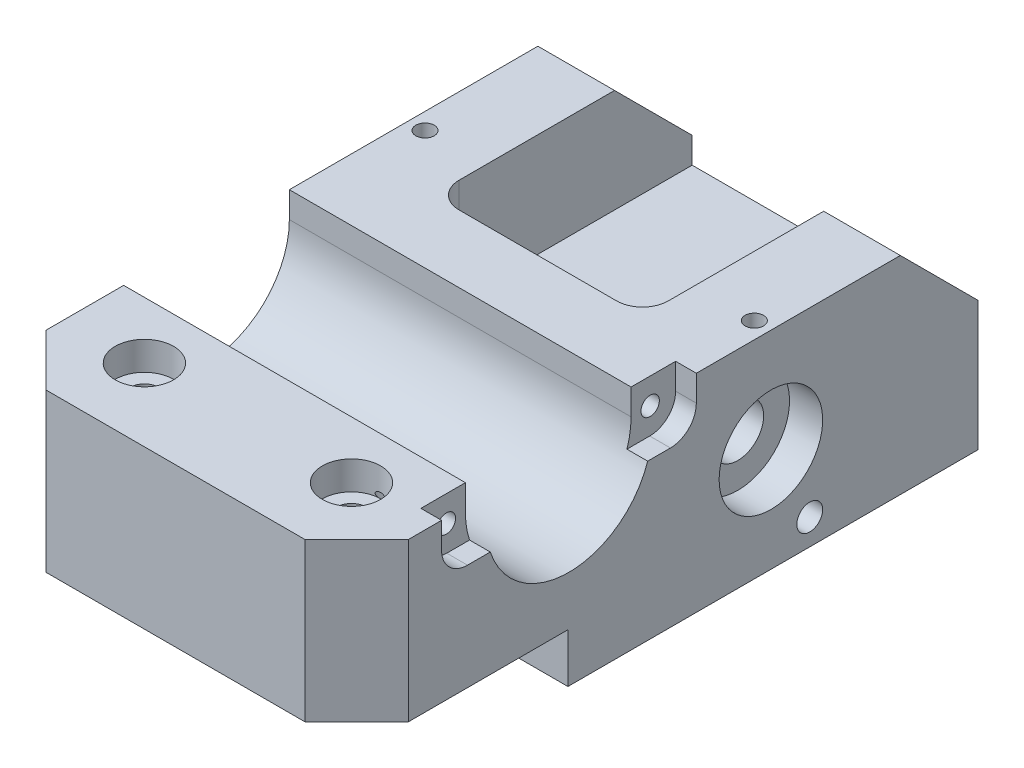
SolidWorks part; units mm, degrees
material "Nylon 6/10"
ref_plane "Front Plane" through (0, 0, 0) normal (0, 0, 1) x (1, 0, 0)
ref_plane "Top Plane" through (0, 0, 0) normal (0, 1, 0) x (1, 0, 0)
ref_plane "Right Plane" through (0, 0, 0) normal (1, 0, 0) x (0, 0, -1)
sketch "Sketch1" plane through (0, 0, 0) normal (0, 1, 0) x (1, 0, 0)
  line L1 (-22.225, -38.1) -> (22.225, -38.1)
  line L2 (-22.225, -38.1) -> (-22.225, 38.1)
  line L3 (-22.225, 38.1) -> (22.225, 38.1)
  line L4 (22.225, -38.1) -> (22.225, 38.1)
  line L5 (-22.225, -38.1) -> (22.225, 38.1) construction
  line L6 (-22.225, 38.1) -> (22.225, -38.1) construction
  point P0 (0, 0)
  dimension "D1" = 44.45
  dimension "D2" = 76.2
extrude "Base" add sketch "Sketch1" along normal blind 12.7 and the other way blind 12.7
sketch "Sketch2" plane through (0, 0, -38.1) normal (0, 0, -1) x (-1, 0, 0)
  line L1 (-22.225, -12.7) -> (22.225, -12.7) construction
  circle A0 centre (0, -12.7) radius 4.7625
  dimension "D1" = 9.525
extrude "ShaftGuide" cut sketch "Sketch2" against normal blind 25.4
ref_plane "Plane1" through (0, -12.7, 0) normal (0, -1, 0) x (-1, 0, 0)
sketch "Sketch3" plane through (0, -12.7, 0) normal (0, -1, 0) x (-1, 0, 0)
  line L0 (10.922, -12.192) -> (16.002, -12.192)
  line L1 (22.225, -38.1) -> (-22.225, -38.1) construction
  line L2 (-22.225, -38.1) -> (-22.225, 38.1) construction
  line L3 (0, 0) -> (0, 102.0916) construction
  line L5 (-10.922, -12.192) -> (-10.922, 4.572)
  line L6 (-22.225, -38.1) -> (22.225, -38.1)
  line L7 (-10.922, 4.572) -> (10.922, 4.572)
  line L8 (10.922, -12.192) -> (10.922, 4.572)
  line L10 (-10.922, -12.192) -> (-22.225, -12.192)
  line L11 (-22.225, -38.1) -> (-22.225, -12.192)
  line L13 (22.225, -38.1) -> (22.225, -12.192)
  line L14 (4.7625, 38.1) -> (4.7625, 12.7)
  line L15 (4.7625, 12.7) -> (-4.7625, 12.7)
  line L16 (-4.7625, 12.7) -> (-4.7625, 38.1)
  line L17 (-4.7625, 38.1) -> (-22.225, 38.1)
  line L18 (-22.225, 38.1) -> (-22.225, -38.1)
  line L19 (-22.225, -38.1) -> (22.225, -38.1)
  line L20 (22.225, -38.1) -> (22.225, 38.1)
  line L21 (22.225, 38.1) -> (4.7625, 38.1)
  line L23 (22.225, 38.1) -> (22.225, -38.1) construction
  line L25 (-4.7625, 38.1) -> (-22.225, 38.1) construction
  line L26 (22.225, -12.192) -> (16.002, -12.192)
  line L28 (22.225, -38.1) -> (22.225, 38.1) construction
  line L29 (22.225, 38.1) -> (4.7625, 38.1) construction
  dimension "D6" = 21.844
  dimension "D3" = 33.528
  dimension "D7" = 16.764
  dimension "D1" = 0
extrude "ActuatorPlaneCut" cut sketch "Sketch3" against normal blind 6.0325
sketch "Sketch5" plane through (0, 0, 0) normal (0, 1, 0) x (1, 0, 0)
  line L1 (12.827, 19.05) -> (-12.827, 19.05)
  line L2 (12.827, 6.35) -> (12.827, 19.05)
  line L3 (12.827, 6.35) -> (-12.827, 6.35)
  line L4 (0, 0) -> (0, 121.8983) construction
  line L5 (-10.922, 4.572) -> (10.922, 4.572) construction
  line L6 (-12.827, 6.35) -> (-12.827, 19.05)
  point P17 (12.827, 6.35)
  point P20 (12.827, 19.05)
  dimension "D3" = 1.778
  dimension "D1" = 12.7
  dimension "D2" = 25.654
extrude "CenterSlot" cut sketch "Sketch5" along normal through all and the other way through all
fillet "CenterSlotFillet" radius 3.175 4 edges at (-12.827, 0, -19.05) (-12.827, 0, -6.35) (12.827, 0, -6.35) (12.827, 0, -19.05)
sketch "Sketch40" plane through (0, -12.7, 0) normal (0, -1, 0) x (1, 0, 0)
  line L1 (10.922, -8.89) -> (-10.922, -8.89)
  line L2 (10.922, -8.89) -> (10.922, 9.017)
  line L3 (7.747, 12.192) -> (-7.747, 12.192)
  line L4 (-10.922, -8.89) -> (-10.922, 9.017)
  line L6 (10.922, -4.572) -> (10.922, 12.192) construction
  line L7 (-9.652, -6.35) -> (9.652, -6.35) construction
  arc A0 (-7.747, 12.192) -> (-10.922, 9.017) centre (-7.747, 9.017) ccw
  arc A1 (7.747, 12.192) -> (10.922, 9.017) centre (7.747, 9.017) cw
  point P8 (-10.922, 12.192)
  dimension "D1" = 3.175
  dimension "D2" = 2.54
extrude "GearBoxPit" cut sketch "Sketch40" against normal blind 11.176
sketch "Sketch60" plane through (0, 12.7, 0) normal (0, 1, 0) x (1, 0, 0)
  line L0 (22.225, 38.1) -> (-22.225, 38.1) construction
  line L1 (-12.827, 15.875) -> (12.827, 15.875)
  line L2 (-12.827, 15.875) -> (-12.827, 38.1)
  line L3 (-12.827, 38.1) -> (12.827, 38.1)
  line L4 (12.827, 15.875) -> (12.827, 38.1)
  line L5 (12.827, 9.525) -> (12.827, 15.875) construction
extrude "FrontCutaway" cut sketch "Sketch60" against normal blind 12.7
chamfer "ChamferFront" distance 9.525 angle 45 2 edges at (-17.526, 12.7, -38.1) (17.526, 12.7, -38.1)
sketch "Sketch67" plane through (0, -12.7, 0) normal (0, -1, 0) x (-1, 0, 0)
  line L0 (-12.3825, 2.54) -> (12.3825, 2.54) construction
  line L1 (-12.3825, 2.9369) -> (12.3825, 2.9369)
  line L2 (-12.3825, 2.1431) -> (12.3825, 2.1431)
  line L3 (-12.3825, -8.128) -> (12.3825, -8.128) construction
  line L4 (-12.3825, -7.7311) -> (12.3825, -7.7311)
  line L5 (-12.3825, -8.5249) -> (12.3825, -8.5249)
  line L6 (9.652, 6.35) -> (-9.652, 6.35) construction
  line L7 (0, 0.0055) -> (0, 0.7987) construction
  arc A0 (-12.3825, 2.9369) -> (-12.3825, 2.1431) centre (-12.3825, 2.54) ccw
  arc A1 (12.3825, 2.1431) -> (12.3825, 2.9369) centre (12.3825, 2.54) ccw
  arc A2 (-12.3825, -7.7311) -> (-12.3825, -8.5249) centre (-12.3825, -8.128) ccw
  arc A3 (12.3825, -8.5249) -> (12.3825, -7.7311) centre (12.3825, -8.128) ccw
  point P2 (0, 2.54)
  point P9 (0, -8.128)
  dimension "D1" = 0.7937
  dimension "D2" = 3.81
  dimension "D3" = 24.765
  dimension "D4" = 10.668
extrude "GearBoxSlotsH" cut sketch "Sketch67" against normal blind 2.286
sketch "Sketch55" plane through (-22.225, 0, 0) normal (-1, 0, 0) x (0, 0, 1)
  line L0 (-38.1, -12.7) -> (12.192, -12.7) construction
  line L1 (-19.05, -12.7) -> (-19.05, -7.9375) construction
  circle A0 centre (-17.4625, -9.525) radius 1.5875
  dimension "D1" = 3.175
  dimension "D2" = 3.175
extrude "GuideBarHole" cut sketch "Sketch55" against normal through all
sketch "Sketch56" plane through (0, 0, 0) normal (1, 0, 0) x (0, 0, -1)
  line L0 (15.875, -12.7) -> (9.525, -12.7) construction
  line L1 (15.875, -12.7) -> (9.525, -12.7) construction
  line L2 (12.7, -12.7) -> (12.7, 12.7) construction
  line L3 (28.575, 12.7) -> (-38.1, 12.7) construction
  circle A0 centre (12.7, 0) radius 3.175
  dimension "D1" = 6.35
extrude "PitchShaftHole" cut sketch "Sketch56" against normal through all and the other way through all
sketch "Sketch57" plane through (-22.225, 0, 0) normal (-1, 0, 0) x (0, 0, 1)
  circle A0 centre (-12.7, 0) radius 6.35
  circle A1 centre (-12.7, 0) radius 3.175 construction
  dimension "D1" = 12.7
extrude "BearingBoreR" cut sketch "Sketch57" against normal blind 4.064
mirror "BearingBoreL" about plane through (0, 0, 0) normal (1, 0, 0) of "BearingBoreR"
hole_wizard "BearingBoreSetScrews" positions "Sketch59" profile "Sketch58" tap size "#4-40" standard "ANSI Inch" end condition up to next
sketch "Sketch59" plane through (4.3433, 12.7, -10.3044) normal (0, 1, 0) x (1, 0, 0)
  line L5 (-26.5683, 8.7456) -> (-26.5683, -3.9544) construction
  line L6 (-26.5683, 8.7456) -> (-26.5683, -3.9544) construction
  line L7 (-26.5683, 2.3956) -> (17.8817, 2.3956) construction
  line L8 (17.8817, -48.4044) -> (17.8817, 18.2706) construction
  line L10 (-26.5683, 18.2706) -> (-26.5683, -48.4044) construction
  point P0 (-24.5363, 2.3956)
  point P2 (15.8497, 2.3956)
  dimension "D1" = 2.032
  dimension "D2" = 2.032
sketch "Sketch58" plane through (-20.193, 12.7, -12.7) normal (1, 0, 0) x (0, 0, 1)
  line L0 (0, 0) -> (0, 6.35)
  line L1 (0, 6.35) -> (1.1303, 6.35)
  line L2 (1.1303, 6.35) -> (1.1303, 0)
  line L5 (1.1303, 0) -> (0, 0)
  line L11 (0, -6.35) -> (0, 107.95) construction
  dimension "Thru Tap Drill Dia." = 2.2606
  dimension "Thru Tap Drill Depth" = 6.35
cosmetic thread "Hole Thread18" parameters "D2"=2.8448
cosmetic thread "Hole Thread19" parameters "D2"=2.8448
hole_wizard "ToggleAssemHoles" positions "Sketch50" profile "Sketch49" tap size "#6-32" standard "ANSI Inch"
sketch "Sketch50" plane through (0, -12.7, 0) normal (0, -1, 0) x (-1, 0, 0)
  line L1 (4.7625, 38.1) -> (-4.7625, 38.1) construction
  line L2 (0, 0) -> (0, 49.3678) construction
  line L3 (-9.652, 19.05) -> (-4.7625, 19.05) construction
  point P0 (12.7, 31.75)
  point P2 (-12.7, 31.75)
  point P8 (0, 38.1)
  dimension "D1" = 12.7
  dimension "D2" = 12.7
sketch "Sketch49" plane through (-12.7, -12.7, -31.75) normal (1, 0, 0) x (0, 0, -1)
  line L0 (0, 0) -> (0, 10.2107)
  line L1 (0, 10.2107) -> (1.3525, 9.398)
  line L2 (1.3525, 9.398) -> (1.3525, 0)
  line L5 (1.3525, 0) -> (0, 0)
  line L10 (0, 10.2107) -> (-1.3526, 9.398) construction
  line L11 (0, -6.35) -> (0, 107.95) construction
  dimension "Tap Drill Dia." = 2.7051
  dimension "Tap Drill Depth" = 9.398
  dimension "Drill Angle" = 118
cosmetic thread "Hole Thread12" parameters "D1"=9.398, "D2"=3.5052
cosmetic thread "Hole Thread13" parameters "D1"=9.398, "D2"=3.5052
chamfer "BackChamfers" distance 6.35 angle 45 2 edges at (22.225, 3.0162, 38.1) (-22.225, 3.0162, 38.1)
sketch "Sketch62" plane through (-22.225, 0, 0) normal (-1, 0, 0) x (0, 0, 1)
  line L0 (-38.1, -12.7) -> (-38.1, 3.175) construction
  line L1 (-28.575, 12.7) -> (31.75, 12.7) construction
  line L2 (1.905, 9.525) -> (1.905, 12.7)
  line L3 (22.225, 9.525) -> (22.225, 12.7)
  line L4 (22.225, 12.7) -> (1.905, 12.7)
  arc A0 (1.905, 9.525) -> (22.225, 9.525) centre (12.065, 9.525) ccw
  dimension "D1" = 20.32
  dimension "D2" = 50.165
  dimension "D3" = 3.175
extrude "PitchMotorSlot" cut sketch "Sketch62" against normal through all
sketch "Sketch63" plane through (22.225, 0, 0) normal (-1, 0, 0) x (0, 0, 1)
  line L1 (-3.556, 12.7) -> (27.686, 12.7)
  line L2 (-3.556, 12.7) -> (-3.556, 9.525)
  line L3 (-0.381, 6.35) -> (24.511, 6.35)
  line L4 (27.686, 12.7) -> (27.686, 9.525)
  line L5 (22.225, 12.7) -> (1.905, 12.7) construction
  arc A0 (24.511, 6.35) -> (27.686, 9.525) centre (24.511, 9.525) ccw
  arc A1 (-0.381, 6.35) -> (-3.556, 9.525) centre (-0.381, 9.525) cw
  point P4 (12.065, 12.7)
  dimension "D3" = 3.175
  dimension "D1" = 31.242
  dimension "D2" = 6.35
extrude "PitchMotorMountingSlots" cut sketch "Sketch63" along normal blind 2.54
hole_wizard "PitchMotorMountingHoles" positions "Sketch65" profile "Sketch64" tap size "#4-40" standard "ANSI Inch"
sketch "Sketch65" plane through (19.685, 0, 0) normal (1, 0, 0) x (0, 0, -1)
  line L0 (-27.686, 12.7) -> (-22.225, 12.7) construction
  line L3 (-22.225, 12.7) -> (-1.905, 12.7) construction
  line L5 (-12.065, 12.7) -> (-12.065, 7.4827) construction
  point P0 (-24.5618, 9.525)
  point P2 (0.4318, 9.525)
  dimension "D1" = 3.175
  dimension "D2" = 24.9936
sketch "Sketch64" plane through (19.685, 9.525, 24.5618) normal (0, 1, 0) x (0, 0, -1)
  line L0 (0, 0) -> (0, 8.2738)
  line L1 (0, 8.2738) -> (1.1303, 7.5946)
  line L2 (1.1303, 7.5946) -> (1.1303, 0)
  line L5 (1.1303, 0) -> (0, 0)
  line L10 (0, 8.2738) -> (-1.1303, 7.5946) construction
  line L11 (0, -6.35) -> (0, 107.95) construction
  dimension "Tap Drill Dia." = 2.2606
  dimension "Tap Drill Depth" = 7.5946
  dimension "Drill Angle" = 118
cosmetic thread "Hole Thread20" parameters "D1"=7.5946, "D2"=2.8448
cosmetic thread "Hole Thread21" parameters "D1"=7.5946, "D2"=2.8448
hole_wizard "GearBoxMountingHoles" positions "Sketch69" profile "Sketch68" tap size "#6-32" standard "ANSI Inch"
sketch "Sketch69" plane through (0, -12.7, 0) normal (0, -1, 0) x (-1, 0, 0)
  line L0 (-12.3825, 2.1431) -> (-10.922, 2.1431) construction
  line L1 (-10.922, -7.7311) -> (-12.3825, -7.7311) construction
  line L2 (-18.542, 2.1431) -> (-10.922, 2.1431) construction
  line L3 (-10.922, -7.7311) -> (-18.542, -7.7311) construction
  line L4 (-14.732, -7.7311) -> (-14.732, 2.1431) construction
  line L6 (0, 0) -> (0, 15.1935) construction
  point P0 (-14.732, -2.794)
  point P2 (14.732, -2.794)
  dimension "D1" = 7.62
sketch "Sketch68" plane through (14.732, -12.7, 2.794) normal (1, 0, 0) x (0, 0, -1)
  line L0 (0, 0) -> (0, 10.2107)
  line L1 (0, 10.2107) -> (1.3525, 9.398)
  line L2 (1.3525, 9.398) -> (1.3525, 0)
  line L5 (1.3525, 0) -> (0, 0)
  line L10 (0, 10.2107) -> (-1.3526, 9.398) construction
  line L11 (0, -6.35) -> (0, 107.95) construction
  dimension "Tap Drill Dia." = 2.7051
  dimension "Tap Drill Depth" = 9.398
  dimension "Drill Angle" = 118
hole_wizard "CapMountingHoles" positions "Sketch74" profile "Sketch73" counterbore size "#6" standard "ANSI Inch" end condition through all
sketch "Sketch74" plane through (-0.8379, 12.7, 8.6337) normal (0, -1, 0) x (-1, 0, 0)
  line L8 (-0.8379, -1002.5128) -> (-0.8379, 48997.4872) construction
  line L9 (15.0371, -29.4663) -> (-16.7129, -29.4663) construction
  point P0 (-13.5379, -20.5763)
  point P2 (11.8621, -20.5763)
  dimension "D1" = 25.4
  dimension "D2" = 8.89
sketch "Sketch73" plane through (12.7, 12.7, 29.21) normal (1, 0, 0) x (0, 0, 1)
  line L0 (0, 0) -> (0, 25.4)
  line L1 (0, 25.4) -> (1.8288, 25.4)
  line L3 (1.8288, 25.4) -> (1.8288, 3.5052)
  line L4 (1.8288, 3.5052) -> (3.5725, 3.5052)
  line L5 (3.5725, 3.5052) -> (3.5725, 0)
  line L7 (3.5725, 0) -> (0, 0)
  line L11 (0, -6.35) -> (0, 107.95) construction
  dimension "Thru Hole Dia." = 3.6576
  dimension "Thru Hole Depth" = 25.4
  dimension "C'Bore Dia." = 7.145
  dimension "C'Bore Depth" = 3.5052
